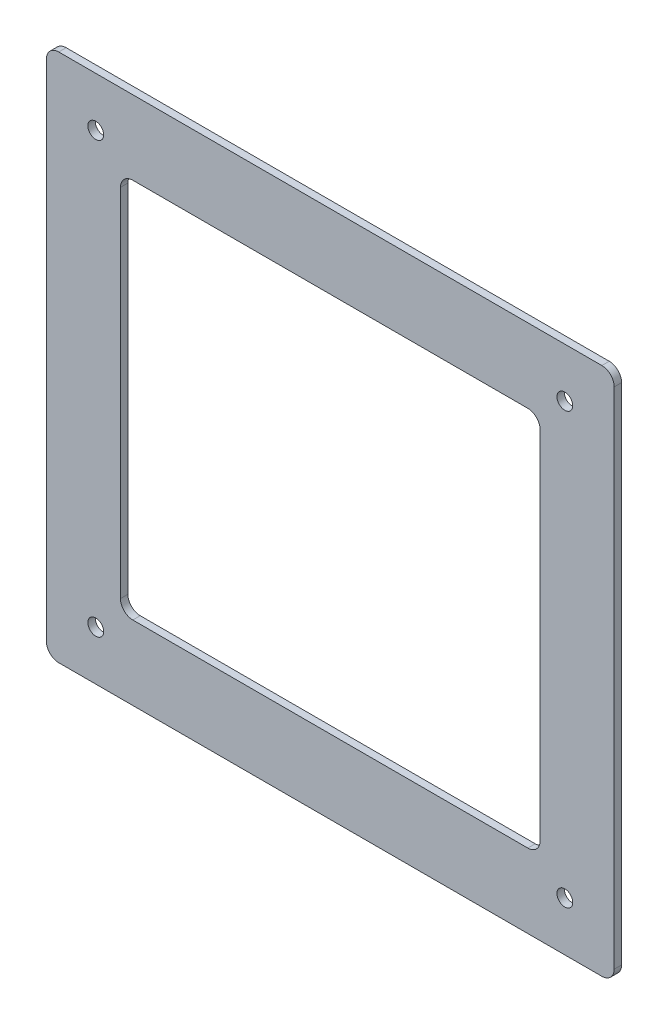
SolidWorks part; units mm, degrees
ref_plane "前视基准面" through (0, 0, 0) normal (0, 0, 1) x (1, 0, 0)
ref_plane "上视基准面" through (0, 0, 0) normal (0, 1, 0) x (1, 0, 0)
ref_plane "右视基准面" through (0, 0, 0) normal (1, 0, 0) x (0, 0, -1)
sketch "草图1" plane through (0, 0, 0) normal (0, 0, 1) x (1, 0, 0)
  line L1 (85, -77.125) -> (-85, -77.125)
  line L2 (85, -77.125) -> (85, 77.125)
  line L3 (85, 77.125) -> (-85, 77.125)
  line L4 (-85, -77.125) -> (-85, 77.125)
  line L5 (85, -77.125) -> (-85, 77.125) construction
  line L6 (85, 77.125) -> (-85, -77.125) construction
  line L7 (115, -107.125) -> (-115, -107.125)
  line L8 (115, -107.125) -> (115, 107.125)
  line L9 (115, 107.125) -> (-115, 107.125)
  line L10 (-115, -107.125) -> (-115, 107.125)
  line L11 (115, -107.125) -> (-115, 107.125) construction
  line L12 (115, 107.125) -> (-115, -107.125) construction
  point P0 (0, 0)
  point P6 (0, 0)
  dimension "D1" = 30
  dimension "D2" = 30
  dimension "D3" = 154.25
  dimension "D4" = 170
extrude "凸台-拉伸1" add sketch "草图1" along normal blind 3
fillet "圆角1" radius 5 8 edges at (85, -77.125, 1.5) (-115, 107.125, 1.5) (-85, 77.125, 1.5) (115, -107.125, 1.5) (-115, -107.125, 1.5) (85, 77.125, 1.5) (115, 107.125, 1.5) (-85, -77.125, 1.5)
sketch "草图2" plane through (0, 0, 3) normal (0, 0, 1) x (1, 0, 0)
  line L0 (80, 77.125) -> (-80, 77.125) construction
  line L1 (-85, 72.125) -> (-85, -72.125) construction
  line L2 (85, -72.125) -> (85, 72.125) construction
  line L3 (-80, -77.125) -> (80, -77.125) construction
  point P0 (-95, 87.125)
  point P1 (-95, -87.125)
  point P2 (95, -87.125)
  point P3 (95, 87.125)
  dimension "D1" = 10
  dimension "D2" = 10
  dimension "D3" = 10
  dimension "D4" = 10
  dimension "D5" = 10
  dimension "D6" = 10
  dimension "D7" = 10
  dimension "D8" = 10
hole_wizard "Ø6.4 (6.4) 直径孔1" positions "草图3" profile "草图4" hole size "Ø6.4" standard "GB" end condition up to next
sketch "草图3" plane through (0, 0, 3) normal (0, 0, 1) x (1, 0, 0)
  point P0 (-95, 87.125)
  point P3 (95, 87.125)
  point P6 (95, -87.125)
  point P9 (-95, -87.125)
sketch "草图4" plane through (-95, 87.125, 3) normal (1, 0, 0) x (0, -1, 0)
  line L0 (0, 0) -> (0, 3)
  line L1 (0, 3) -> (3.2, 3)
  line L2 (3.2, 3) -> (3.2, 0)
  line L5 (3.2, 0) -> (0, 0)
  line L11 (0, -6.35) -> (0, 107.95) construction
  dimension "通孔孔直径" = 6.4
  dimension "通孔孔深度" = 3
